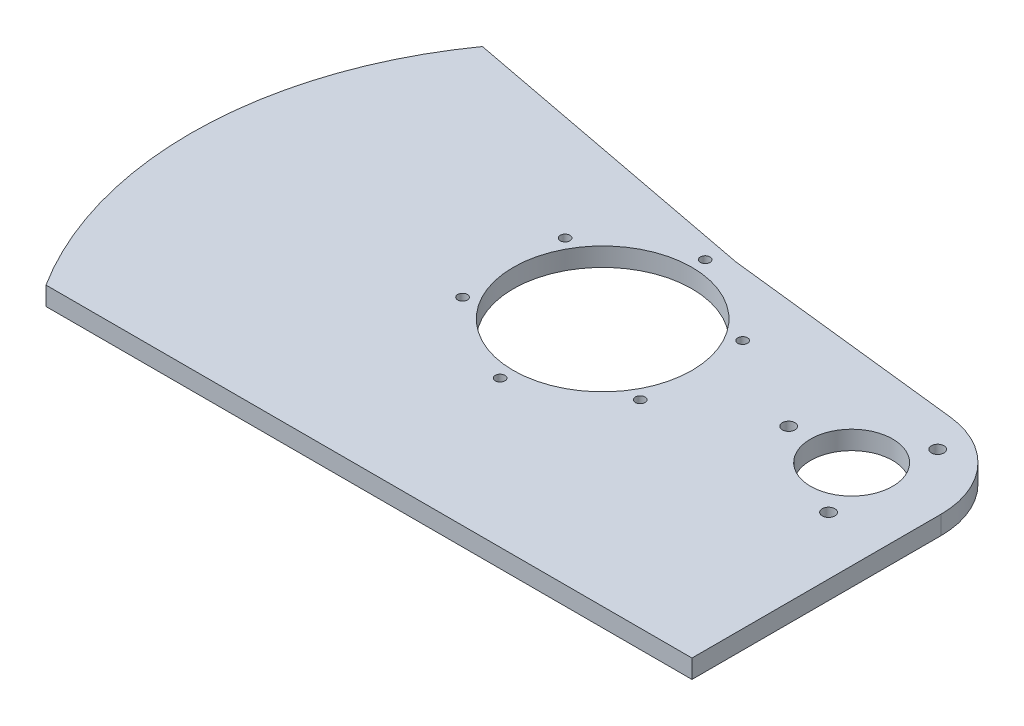
SolidWorks part; units mm, degrees
material "6061 Alloy"
ref_plane "Front Plane" through (0, 0, 0) normal (0, 0, 1) x (1, 0, 0)
ref_plane "Top Plane" through (0, 0, 0) normal (0, 1, 0) x (1, 0, 0)
ref_plane "Right Plane" through (0, 0, 0) normal (1, 0, 0) x (0, 0, -1)
sketch "Sketch1" plane through (0, 0, 0) normal (0, 1, 0) x (1, 0, 0)
  line L0 (4.4706, 39.7494) -> (88.4088, 30.3089)
  line L1 (-40, 40) -> (115.5, 40)
  line L2 (-40, 40) -> (-40, -85)
  line L3 (-40, -85) -> (115.5, -85)
  line L4 (115.5, 40) -> (115.5, -85)
  line L5 (-40, 40) -> (115.5, -85) construction
  line L6 (-40, -85) -> (115.5, 40) construction
  line L7 (-101.026, 60) -> (7.4977, 39.291)
  line L8 (-40, -85) -> (-105, -85)
  circle A0 centre (0, 0) radius 40
  circle A1 centre (0, 0) radius 30.5
  circle A2 centre (85, 0) radius 14
  circle A3 centre (85, 0) radius 30.5
  circle A5 centre (0, 0) radius 117.5 construction
  arc A6 (-101.026, 60) -> (-105, -85) centre (4.8344, -15.4558) ccw
  point P4 (37.75, -22.5)
  dimension "D3" = 80
  dimension "D4" = 61
  dimension "D5" = 61
  dimension "D6" = 28
  dimension "D2" = 235
  dimension "D8" = 130
  dimension "D1" = 85
  dimension "D7" = 85
  dimension "D9" = 65
  dimension "D10" = 20
extrude "Boss-Extrude1" add sketch "Sketch1" along normal mid plane 6.35 contours A0 L0 L1 | A0 L0 | A3 L0 A0 L2 L3 L4 | A0 A1 | A0 L1 L2 | L2 L1 | A3 A2 region at (3.6102, 0, -39.8797) region at (5.9894, 0, -39.555) region at (5.8191, 0, -38.4306) region at (41.203, 0, 46.4586) region at (-31.0653, 0, -31.0653) region at (-79.0131, 0, 14.358) region at (107.0969, 0, -19.751)
hole_wizard "M4x0.7 Tapped Hole1" positions "Sketch4" profile "Sketch5" tap size "M4x0.7" standard "ANSI Metric" end condition up to next
sketch "Sketch4" plane through (0, 3.175, 0) normal (0, 1, 0) x (1, 0, 0)
  line L0 (0, 0) -> (0, 35)
  line L1 (0, 0) -> (30.3109, 17.5)
  line L2 (0, 0) -> (30.3109, -17.5)
  line L3 (0, 0) -> (0, -35)
  line L4 (0, 0) -> (-30.3109, -17.5)
  line L5 (0, 0) -> (-30.3109, 17.5)
  point P5 (0, 35)
  point P16 (30.3109, 17.5)
  point P17 (30.3109, -17.5)
  point P18 (0, -35)
  point P19 (-30.3109, -17.5)
  point P20 (-30.3109, 17.5)
  dimension "D1" = 35
  dimension "D2" = 6
sketch "Sketch5" plane through (-30.3109, 3.175, -17.5) normal (1, 0, 0) x (0, 0, 1)
  line L0 (0, 0) -> (0, 6.35)
  line L1 (0, 6.35) -> (1.65, 6.35)
  line L2 (1.65, 6.35) -> (1.65, 0)
  line L5 (1.65, 0) -> (0, 0)
  line L11 (0, -6.35) -> (0, 107.95) construction
  dimension "Thru Tap Drill Dia." = 3.3
  dimension "Thru Tap Drill Depth" = 6.35
cosmetic thread "Hole Thread1" parameters "D2"=4
cosmetic thread "Hole Thread2" parameters "D2"=4
cosmetic thread "Hole Thread3" parameters "D2"=4
cosmetic thread "Hole Thread4" parameters "D2"=4
cosmetic thread "Hole Thread5" parameters "D2"=4
cosmetic thread "Hole Thread6" parameters "D2"=4
hole_wizard "M4 Clearance Hole1" positions "Sketch6" profile "Sketch7" hole size "M4" standard "ANSI Metric" end condition up to next
sketch "Sketch6" plane through (0, 3.175, 0) normal (0, 1, 0) x (1, 0, 0)
  line L0 (85, 0) -> (95.75, 18.6195)
  line L1 (85, 0) -> (95.75, -18.6195)
  line L2 (85, 0) -> (63.5, 0)
  point P2 (95.75, 18.6195)
  point P10 (95.75, -18.6195)
  point P11 (63.5, 0)
  dimension "D1" = 21.5
  dimension "D2" = 3
sketch "Sketch7" plane through (63.5, 3.175, 0) normal (1, 0, 0) x (0, 0, 1)
  line L0 (0, 0) -> (0, 6.35)
  line L1 (0, 6.35) -> (2.15, 6.35)
  line L2 (2.15, 6.35) -> (2.15, 0)
  line L5 (2.15, 0) -> (0, 0)
  line L11 (0, -6.35) -> (0, 107.95) construction
  dimension "Thru Hole Dia." = 4.3
  dimension "Thru Hole Depth" = 6.35
